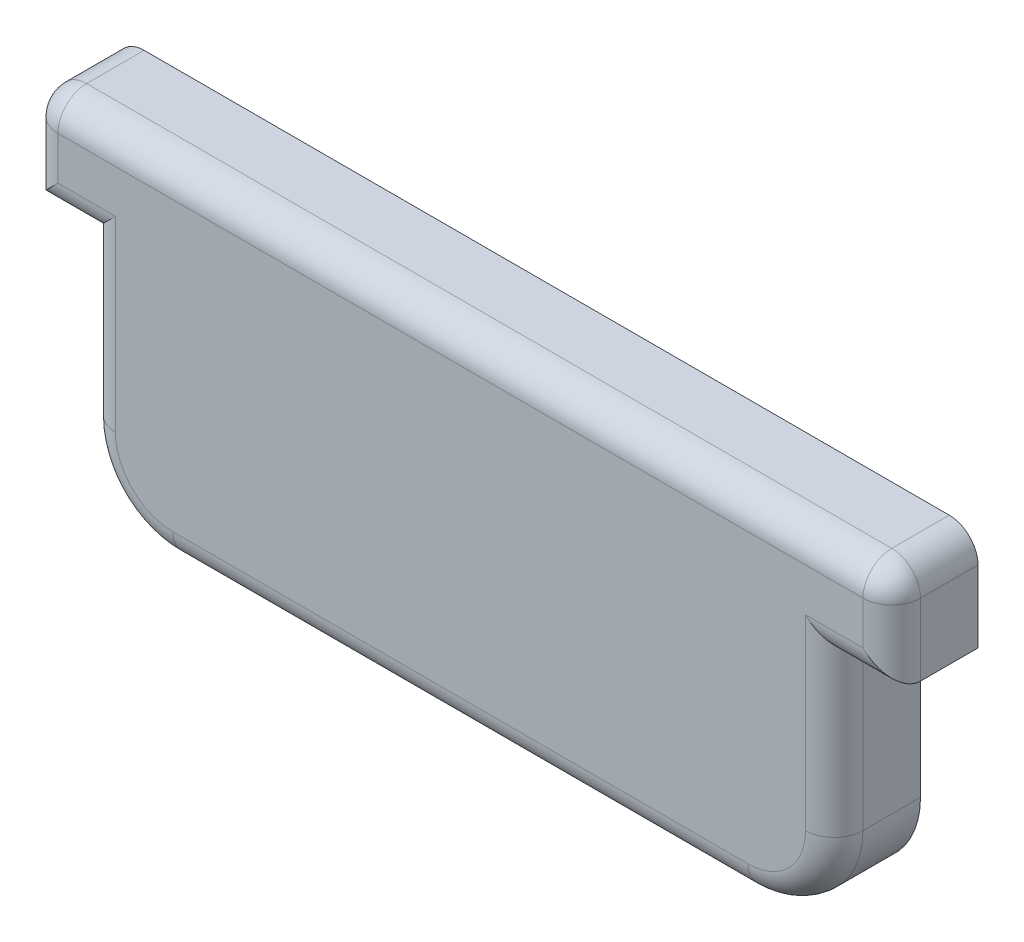
SolidWorks part; units mm, degrees
ref_plane "Front Plane" through (0, 0, 0) normal (0, 0, 1) x (1, 0, 0)
ref_plane "Top Plane" through (0, 0, 0) normal (0, 1, 0) x (1, 0, 0)
ref_plane "Right Plane" through (0, 0, 0) normal (1, 0, 0) x (0, 0, -1)
sketch "Sketch1" plane through (0, 0, 0) normal (0, 0, 1) x (1, 0, 0)
  line L3 (40, 52.5) -> (40, 80)
  line L4 (-70, 42.5) -> (30, 42.5)
  line L5 (-80, 80) -> (-80, 52.5)
  line L6 (-85, 80) -> (-85, 52.5)
  line L7 (-70, 37.5) -> (30, 37.5)
  line L8 (45, 52.5) -> (45, 80)
  line L9 (45, 80) -> (40, 80)
  line L10 (-85, 80) -> (-80, 80)
  arc A2 (30, 42.5) -> (40, 52.5) centre (30, 52.5) ccw
  arc A3 (-80, 52.5) -> (-70, 42.5) centre (-70, 52.5) ccw
  arc A4 (-85, 52.5) -> (-70, 37.5) centre (-70, 52.5) ccw
  arc A5 (30, 37.5) -> (45, 52.5) centre (30, 52.5) ccw
  dimension "D1" = 5
extrude "Boss-Extrude2" add sketch "Sketch1" along normal blind 10
sketch "Sketch2" plane through (0, 0, 10) normal (0, 0, 1) x (1, 0, 0)
  line L0 (45, 52.5) -> (45, 80) construction
  line L1 (-85, 80) -> (-85, 52.5) construction
  line L2 (-70, 37.5) -> (30, 37.5) construction
  line L3 (45, 52.5) -> (45, 80)
  line L4 (-85, 80) -> (-85, 52.5)
  line L5 (-70, 37.5) -> (30, 37.5)
  line L6 (45, 80) -> (-85, 80)
  arc A0 (30, 37.5) -> (45, 52.5) centre (30, 52.5) ccw construction
  arc A1 (-85, 52.5) -> (-70, 37.5) centre (-70, 52.5) ccw construction
  arc A2 (30, 37.5) -> (45, 52.5) centre (30, 52.5) ccw
  arc A3 (-85, 52.5) -> (-70, 37.5) centre (-70, 52.5) ccw
extrude "Boss-Extrude3" add sketch "Sketch2" along normal blind 5
fillet "Fillet1" radius 10 5 edges at (-77.0711, 45.4289, 10) (-20, 42.5, 10) (37.0711, 45.4289, 10)
sketch "Sketch3" plane through (0, 80, 0) normal (0, 1, 0) x (1, 0, 0)
  line L0 (-80, 0) -> (-85, 0) construction
  line L1 (55, -15) -> (-95, -15)
  line L2 (55, -15) -> (55, 0)
  line L3 (55, 0) -> (-95, 0)
  line L4 (-95, -15) -> (-95, 0)
  line L5 (55, -15) -> (-95, 0) construction
  line L6 (55, 0) -> (-95, -15) construction
  line L7 (-20, -7.5) -> (-20, -15) construction
  line L8 (45, -15) -> (-85, -15) construction
  point P0 (-20, -7.5)
  dimension "D1" = 150
extrude "Boss-Extrude4" add sketch "Sketch3" along normal blind 17.5 contours L3 L4 L1 L2
sketch "Sketch5" plane through (0, 0, 0) normal (0, 0, -1) x (-1, 0, 0)
  line L0 (-55, 80) -> (-45, 80) construction
  line L1 (-51, 80) -> (0, 80)
  line L2 (-51, 80) -> (-51, 94.2307)
  line L3 (-51, 94.2307) -> (0, 94.2307)
  line L4 (0, 80) -> (0, 94.2307)
  line L5 (20, 97.5) -> (20, 80) construction
  line L6 (-55, 97.5) -> (95, 97.5) construction
  line L7 (-40, 80) -> (80, 80) construction
  line L8 (-30, 80) -> (70, 80) construction
  line L9 (40, 80) -> (91, 80)
  line L10 (40, 80) -> (40, 94.2307)
  line L11 (40, 94.2307) -> (91, 94.2307)
  line L12 (91, 80) -> (91, 94.2307)
  dimension "D1" = 20
  dimension "D2" = 51
  dimension "D3" = 20
  dimension "D4" = 51
extrude "Cut-Extrude1" cut sketch "Sketch5" against normal blind 3
fillet "Fillet2" radius 5 12 edges at (-20, 37.5, 15) (-80.6066, 41.8934, 15) (-95, 88.75, 15) (-20, 97.5, 15) (55, 88.75, 15) (40.6066, 41.8934, 15) (-95, 97.5, 7.5) (55, 97.5, 7.5)
